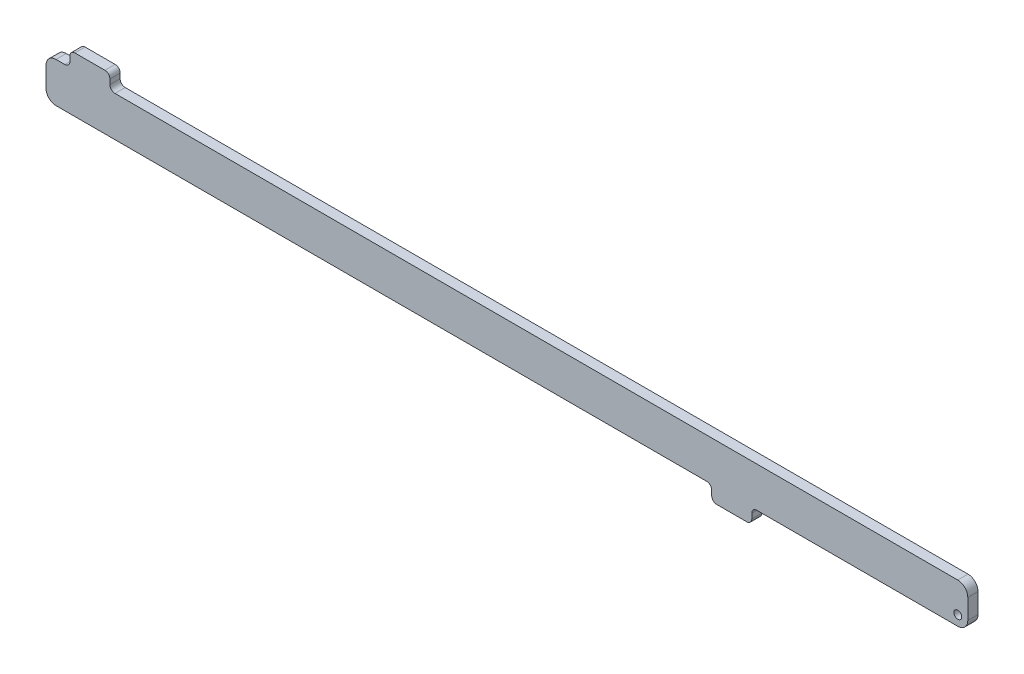
SolidWorks part; units mm, degrees
material "PC High Viscosity"
ref_plane "Front Plane" through (0, 0, 0) normal (0, 0, 1) x (1, 0, 0)
ref_plane "Top Plane" through (0, 0, 0) normal (0, 1, 0) x (1, 0, 0)
ref_plane "Right Plane" through (0, 0, 0) normal (1, 0, 0) x (0, 0, -1)
sketch "Sketch1" plane through (0, 0, 0) normal (0, 0, 1) x (1, 0, 0)
  line L1 (0, 0) -> (40.5308, 0)
  line L2 (0, 0) -> (0, 25.4)
  line L3 (0, 25.4) -> (15.1307, 25.4)
  line L4 (584.2, 0) -> (584.2, 25.4)
  line L5 (15.1307, 34.925) -> (40.5307, 34.925)
  line L6 (40.5307, 34.925) -> (40.5307, 25.4)
  line L7 (15.1307, 34.925) -> (15.1307, 25.4)
  line L11 (584.2, 10.0162) -> (577.85, 13.6823) construction
  line L12 (577.85, 13.6823) -> (571.5, 10.0162) construction
  line L13 (571.5, 10.0162) -> (571.5, 2.6838) construction
  line L14 (571.5, 2.6838) -> (577.85, -0.9823) construction
  line L15 (577.85, -0.9823) -> (584.2, 2.6838) construction
  line L16 (584.2, 2.6838) -> (584.2, 10.0162) construction
  line L19 (40.5307, 25.4) -> (584.2, 25.4)
  line L20 (40.5308, 0) -> (421.9033, 0)
  line L21 (447.3033, 0) -> (447.3033, -9.525)
  line L22 (447.3033, -9.525) -> (421.9033, -9.525)
  line L23 (421.9033, -9.525) -> (421.9033, 0)
  line L24 (447.3033, 0) -> (584.2, 0)
  circle A0 centre (577.85, 6.35) radius 2.4892
  circle A1 centre (577.85, 6.35) radius 6.35 construction
  dimension "D5" = 4.9784
  dimension "D6" = 9.525
  dimension "D7" = 12.7
  dimension "D1" = 584.2
  dimension "D2" = 25.4
  dimension "D3" = 25.4
  dimension "D4" = 40.5307
  dimension "D8" = 421.9033
extrude "Boss-Extrude1" add sketch "Sketch1" along normal blind 6.477 contours L6 L5 L3 | L1 L4 L3 L2 A0 | L1 region at (289.8115, 12.7081, 0)
fillet "Fillet2" radius 6.35 4 edges at (0, 0, 3.2385) (0, 25.4, 3.2385) (584.2, 0, 3.2385) (584.2, 25.4, 3.2385)
sketch "Sketch2" plane through (0, 0, 6.477) normal (0, 0, 1) x (1, 0, 0)
  line L0 (6.35, 25.4) -> (15.1307, 25.4) construction
  line L1 (584.2, 19.05) -> (584.2, 6.35) construction
  circle A0 centre (546.1, 12.7) radius 2.0193
  dimension "D1" = 4.0386
  dimension "D2" = 12.7
  dimension "D3" = 38.1
fillet "Fillet3" radius 3.175 8 edges at (15.1307, 25.4, 3.2385) (15.1307, 34.925, 3.2385) (40.5307, 34.925, 3.2385) (40.5307, 25.4, 3.2385) (421.9033, 0, 3.2385) (421.9033, -9.525, 3.2385) (447.3033, -9.525, 3.2385) (447.3033, 0, 3.2385)
